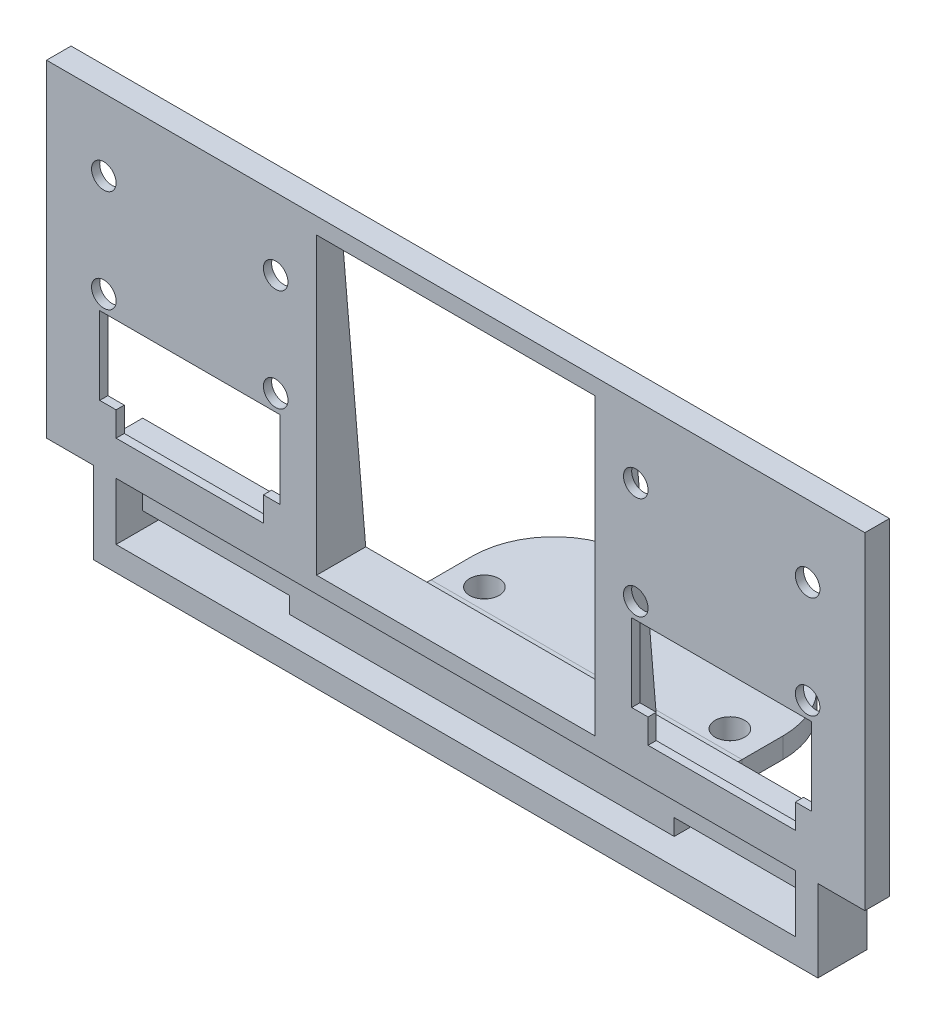
SolidWorks part; units mm, degrees
ref_plane "Front Plane" through (0, 0, 0) normal (0, 0, 1) x (1, 0, 0)
ref_plane "Top Plane" through (0, 0, 0) normal (0, 1, 0) x (1, 0, 0)
ref_plane "Right Plane" through (0, 0, 0) normal (1, 0, 0) x (0, 0, -1)
sketch "Sketch1" plane through (0, 0, 0) normal (0, 0, 1) x (1, 0, 0)
  line L0 (0, -20) -> (0, 20) construction
  line L1 (-50, -20) -> (50, -20)
  line L2 (-50, -20) -> (-50, 20)
  line L3 (-50, 20) -> (50, 20)
  line L4 (50, -20) -> (50, 20)
  line L5 (-50, -20) -> (50, 20) construction
  line L6 (-50, 20) -> (50, -20) construction
  line L7 (0, 0) -> (-32.5, 0) construction
  line L8 (-32.5, 0) -> (-32.5, 13.286) construction
  line L9 (-41.8988, 5) -> (-23.0802, 5) construction
  line L10 (-32.5, 20) -> (-32.5, -20) construction
  line L11 (41.5, -15.75) -> (23.5, -12.75) construction
  line L12 (-41.5, -12.75) -> (-23.5, -12.75)
  line L13 (-41.5, -12.75) -> (-41.5, -15.75)
  line L14 (-41.5, -15.75) -> (-23.5, -15.75)
  line L15 (-23.5, -12.75) -> (-23.5, -15.75)
  line L16 (-41.5, -12.75) -> (-23.5, -15.75) construction
  line L17 (-41.5, -15.75) -> (-23.5, -12.75) construction
  line L18 (41.5, -12.75) -> (23.5, -15.75) construction
  line L19 (41.8988, 5) -> (23.0802, 5) construction
  line L20 (32.5, 0) -> (32.5, 13.286) construction
  line L21 (23.5, -12.75) -> (23.5, -15.75)
  line L22 (41.5, -15.75) -> (23.5, -15.75)
  line L23 (41.5, -12.75) -> (41.5, -15.75)
  line L24 (41.5, -12.75) -> (23.5, -12.75)
  circle A0 centre (-22, 11.25) radius 1.5
  circle A1 centre (-43, 11.25) radius 1.5
  circle A2 centre (-43, -1.25) radius 1.5
  circle A3 centre (-22, -1.25) radius 1.5
  circle A4 centre (22, -1.25) radius 1.5
  circle A5 centre (43, -1.25) radius 1.5
  circle A6 centre (43, 11.25) radius 1.5
  circle A7 centre (22, 11.25) radius 1.5
  point P0 (0, 0)
  point P23 (-32.5, -14.25)
  point P44 (32.5, -14.25)
  dimension "D4" = 3
  dimension "D1" = 100
  dimension "D2" = 40
  dimension "D3" = 32.5
  dimension "D5" = 10.5
  dimension "D6" = 6.25
  dimension "D7" = 5
  dimension "D8" = 18
  dimension "D9" = 3
  dimension "D10" = 13
extrude "Boss-Extrude1" add sketch "Sketch1" along normal blind 3
sketch "Sketch2" plane through (0, 0, 0) normal (0, 0, -1) x (-1, 0, 0)
  line L0 (-50, 20) -> (50, 20) construction
  line L1 (-48, -18) -> (-1.5, -18)
  line L2 (-48, -18) -> (-48, 18)
  line L3 (-48, 18) -> (-1.5, 18)
  line L4 (48, -18) -> (48, 18)
  line L5 (-48, -18) -> (48, 18) construction
  line L6 (-48, 18) -> (48, -18) construction
  line L7 (-50, -20) -> (-50, 20) construction
  line L8 (-1.5, 18) -> (-1.5, -18)
  line L9 (1.5, -18) -> (1.5, 18)
  line L10 (1.5, 18) -> (48, 18)
  line L11 (1.5, -18) -> (48, -18)
  point P0 (0, 0)
  dimension "D1" = 2
  dimension "D2" = 2
  dimension "D3" = 1.5
  dimension "D4" = 1.5
extrude "Cut-Extrude1" cut sketch "Sketch2" against normal offset from surface (2 mm away) 1 up to face at (-32.5, -14.25, 3)
sketch "Sketch3" plane through (0, -20, 0) normal (0, -1, 0) x (-1, 0, 0)
  line L0 (50, 0) -> (-50, 0) construction
  line L1 (44.25, 0) -> (-44.25, 0)
  line L2 (44.25, 0) -> (44.25, 3)
  line L3 (44.25, 3) -> (-44.25, 3)
  line L4 (-44.25, 0) -> (-44.25, 3)
  line L5 (0, 3) -> (0, 0) construction
  dimension "D1" = 0
  dimension "D2" = 44.25
  dimension "D3" = 3
extrude "Boss-Extrude2" add sketch "Sketch3" against normal up to surface (2 mm away) up to face at (24.75, -18, 1)
sketch "Sketch4" plane through (0, -20, 0) normal (0, -1, 0) x (1, 0, 0)
  line L0 (-44.25, 0) -> (-44.25, -3) construction
  line L1 (44.25, -3) -> (-44.25, -3)
  line L2 (44.25, -3) -> (44.25, -0.2)
  line L3 (44.25, -0.2) -> (-44.25, -0.2)
  line L4 (-44.25, -3) -> (-44.25, -0.2)
  dimension "D1" = 2.8
extrude "Boss-Extrude3" add sketch "Sketch4" along normal blind 10
sketch "Sketch5" plane through (0, 0, 3) normal (0, 0, 1) x (1, 0, 0)
  line L0 (50, 20) -> (-50, 20) construction
  line L1 (-17, -18) -> (17, -18)
  line L2 (-17, -18) -> (-17, 18)
  line L3 (-17, 18) -> (17, 18)
  line L4 (17, -18) -> (17, 18)
  line L5 (-17, -18) -> (17, 18) construction
  line L6 (-17, 18) -> (17, -18) construction
  circle A0 centre (22, -1.25) radius 1.5 construction
  point P0 (0, 0)
  dimension "D1" = 2
  dimension "D2" = 5
extrude "Cut-Extrude2" cut sketch "Sketch5" against normal through all
sketch "Sketch6" plane through (0, 0, 3) normal (0, 0, 1) x (1, 0, 0)
  line L0 (-32.5, -12.75) -> (-32.5, -8) construction
  line L1 (-23.5, -12.75) -> (-41.5, -12.75) construction
  line L2 (0, -18) -> (0, 18) construction
  line L3 (-43.5, -3.25) -> (-21.5, -3.25)
  line L4 (-43.5, -3.25) -> (-43.5, -12.75)
  line L5 (-43.5, -12.75) -> (-21.5, -12.75)
  line L6 (-21.5, -3.25) -> (-21.5, -12.75)
  line L7 (-43.5, -3.25) -> (-21.5, -12.75) construction
  line L8 (-43.5, -12.75) -> (-21.5, -3.25) construction
  line L9 (-17, -18) -> (17, -18) construction
  line L10 (17, 18) -> (-17, 18) construction
  line L11 (43.5, -12.75) -> (21.5, -3.25) construction
  line L12 (43.5, -3.25) -> (21.5, -12.75) construction
  line L13 (21.5, -3.25) -> (21.5, -12.75)
  line L14 (43.5, -12.75) -> (21.5, -12.75)
  line L15 (43.5, -3.25) -> (21.5, -3.25)
  line L16 (32.5, -12.75) -> (32.5, -8) construction
  line L17 (43.5, -3.25) -> (43.5, -12.75)
  line L18 (-43.5, -12.75) -> (-21.5, -3.25) construction
  dimension "D1" = 22
  dimension "D2" = 9.5
  dimension "D3" = 0
extrude "Cut-Extrude5" cut sketch "Sketch6" against normal through all
sketch "Sketch7" plane through (0, 0, 2) normal (0, 0, -1) x (-1, 0, 0)
  line L0 (48, 18) -> (-48, 18) construction
  line L1 (-17, -18) -> (-18.5, -18)
  line L2 (-17, -18) -> (-17, 18)
  line L3 (-17, 18) -> (-18.5, 18)
  line L4 (-18.5, -18) -> (-18.5, 18)
  line L5 (0, 18) -> (0, -18) construction
  line L6 (-44.25, -18) -> (44.25, -18) construction
  line L7 (18.5, -18) -> (18.5, 18)
  line L8 (17, 18) -> (18.5, 18)
  line L9 (17, -18) -> (17, 18)
  line L10 (17, -18) -> (18.5, -18)
  line L11 (-18.5, -18) -> (-18.5, 18)
  line M12 (-17, -18) -> (-17, 18)
  line M13 (-17, 18) -> (-48, 18)
  line M15 (-48, -18) -> (-17, -18)
  dimension "D1" = 1.5
extrude "Boss-Extrude4" add sketch "Sketch7" along normal up to surface (5 mm away) contours L4 M15 M12 M13 | L9 L10 L7 L8 region at (17.75, 0, 2) region at (-17.75, 0, 2) up to face at (0, -24, -3)
sketch "Sketch8" plane through (18.5, 0, 0) normal (1, 0, 0) x (0, 0, -1)
  line L0 (0, 18) -> (3, -18)
  line L1 (3, -18) -> (3, 18)
  line L2 (3, 18) -> (0, 18)
extrude "Cut-Extrude6" cut sketch "Sketch8" against normal through all
sketch "Sketch9" plane through (0, -20, 0) normal (0, -1, 0) x (1, 0, 0)
  line L0 (0, 3) -> (0, -0.2) construction
  line L1 (-41.5, 2) -> (-23.5, 2)
  line L2 (-41.5, 2) -> (-41.5, 0)
  line L3 (-41.5, 0) -> (-23.5, 0)
  line L4 (-23.5, 2) -> (-23.5, 0)
  line L5 (-41.5, 2) -> (-23.5, 0) construction
  line L6 (-41.5, 0) -> (-23.5, 2) construction
  line L7 (-50, 3) -> (50, 3) construction
  line L8 (44.25, -0.2) -> (-44.25, -0.2) construction
  line L9 (41.5, 0) -> (23.5, 2) construction
  line L10 (41.5, 2) -> (23.5, 0) construction
  line L11 (23.5, 2) -> (23.5, 0)
  line L12 (41.5, 0) -> (23.5, 0)
  line L13 (41.5, 2) -> (41.5, 0)
  line L14 (41.5, 2) -> (23.5, 2)
  point P0 (-32.5, 1)
  point P15 (32.5, 1)
  dimension "D1" = 32.5
  dimension "D2" = 18
  dimension "D3" = 2
  dimension "D4" = 1
extrude "Cut-Extrude7" cut sketch "Sketch9" against normal blind 5
sketch "Sketch10" plane through (0, -30, 0) normal (0, -1, 0) x (1, 0, 0)
  line L0 (0, 0) -> (0, -3) construction
  line L1 (-44.25, -3) -> (44.25, -3) construction
  line L2 (0, -28) -> (0, -3) construction
  line L3 (-19, -3) -> (19, -3)
  line L4 (-19, -3) -> (-19, -28)
  line L5 (-19, -28) -> (19, -28)
  line L6 (19, -3) -> (19, -28)
  dimension "D1" = 38
  dimension "D2" = 25
extrude "Boss-Extrude7" add sketch "Sketch10" against normal blind 2.5
sketch "Sketch11" plane through (0, -30, 0) normal (0, -1, 0) x (1, 0, 0)
  line L0 (0, -28) -> (0, 0) construction
  line L1 (-19, -28) -> (19, -28) construction
  line L2 (-19, -15.5) -> (19, -15.5) construction
  line L3 (-19, -3) -> (-19, -28) construction
  line L4 (19, -28) -> (19, -3) construction
  circle A0 centre (15, -15.5) radius 1.8
  circle A1 centre (-15, -15.5) radius 1.8
  circle A2 centre (0, -23.5) radius 1.8
  circle A3 centre (0, -7.5) radius 1.8
  dimension "D1" = 3.6
  dimension "D4" = 3.6
  dimension "D2" = 15
  dimension "D3" = 8
extrude "Cut-Extrude8" cut sketch "Sketch11" against normal through all
fillet "Fillet1" radius 10 5 edges at (19, -28.75, -28) (-19, -28.75, -28) (0, -27.5, -3)
sketch "Sketch12" plane through (0, -30, 0) normal (0, -1, 0) x (1, 0, 0)
  circle A0 centre (0, -7.5) radius 3.5
  dimension "D1" = 7
extrude "Cut-Extrude10" cut sketch "Sketch12" along normal up to surface (-2.5 mm away) from offset 10 up to face at (0, -27.5, -25.3) offset against normal yes
sketch "Sketch13" plane through (0, 0, -0.2) normal (0, 0, 1) x (1, 0, 0)
  line L0 (-44.25, -25) -> (44.25, -25) construction
  line L1 (-44.25, -30) -> (-44.25, -20) construction
  line L2 (44.25, -30) -> (44.25, -20) construction
  line L3 (0, -20) -> (0, -30) construction
  line L4 (-50, -20) -> (50, -20) construction
  line L5 (44.25, -30) -> (-44.25, -30) construction
  line L6 (32.5, -15.75) -> (32.5, -30) construction
  line L7 (23.5, -15.75) -> (41.5, -15.75) construction
  line L8 (-23.5, -27) -> (-41.5, -25) construction
  line L9 (23.5, -25) -> (41.5, -25)
  line L10 (23.5, -25) -> (23.5, -27)
  line L11 (23.5, -27) -> (41.5, -27)
  line L12 (41.5, -25) -> (41.5, -27)
  line L13 (23.5, -25) -> (41.5, -27) construction
  line L14 (23.5, -27) -> (41.5, -25) construction
  line L15 (-23.5, -25) -> (-41.5, -27) construction
  line L16 (-32.5, -15.75) -> (-32.5, -30) construction
  line L17 (-41.5, -25) -> (-41.5, -27)
  line L18 (-23.5, -27) -> (-41.5, -27)
  line L19 (-23.5, -25) -> (-23.5, -27)
  line L20 (-23.5, -25) -> (-41.5, -25)
  point P12 (32.5, -26)
  point P27 (-32.5, -26)
  dimension "D1" = 2
  dimension "D2" = 1
extrude "Cut-Extrude11" cut sketch "Sketch13" against normal through all
sketch "Sketch14" plane through (0, 0, -0.2) normal (0, 0, 1) x (1, 0, 0)
  line L0 (44.25, -30) -> (-44.25, -30) construction
  line L1 (-44.25, -20) -> (-41.5, -20)
  line L2 (-44.25, -20) -> (-44.25, -30)
  line L3 (-44.25, -30) -> (-41.5, -30)
  line L4 (-41.5, -20) -> (-41.5, -30)
  line L5 (-41.5, -25) -> (-41.5, -27) construction
  line L6 (0, 0) -> (0, -10.7923) construction
  line L7 (41.5, -20) -> (41.5, -30)
  line L8 (44.25, -30) -> (41.5, -30)
  line L9 (44.25, -20) -> (44.25, -30)
  line L10 (44.25, -20) -> (41.5, -20)
extrude "Boss-Extrude8" add sketch "Sketch14" along normal up to surface (3.2 mm away) up to face at (0, 0, 3)
sketch "Sketch15" plane through (0, 0, -0.2) normal (0, 0, 1) x (1, 0, 0)
  line L0 (-41.5, -20) -> (-41.5, -30) construction
  line L1 (-41.5, -27) -> (41.5, -27)
  line L2 (-41.5, -27) -> (-41.5, -30)
  line L3 (-41.5, -30) -> (41.5, -30)
  line L4 (41.5, -27) -> (41.5, -30)
  line L5 (-41.5, -27) -> (-23.5, -27) construction
extrude "Boss-Extrude9" add sketch "Sketch15" along normal up to surface (3.2 mm away) up to face at (0, 0, 3)
